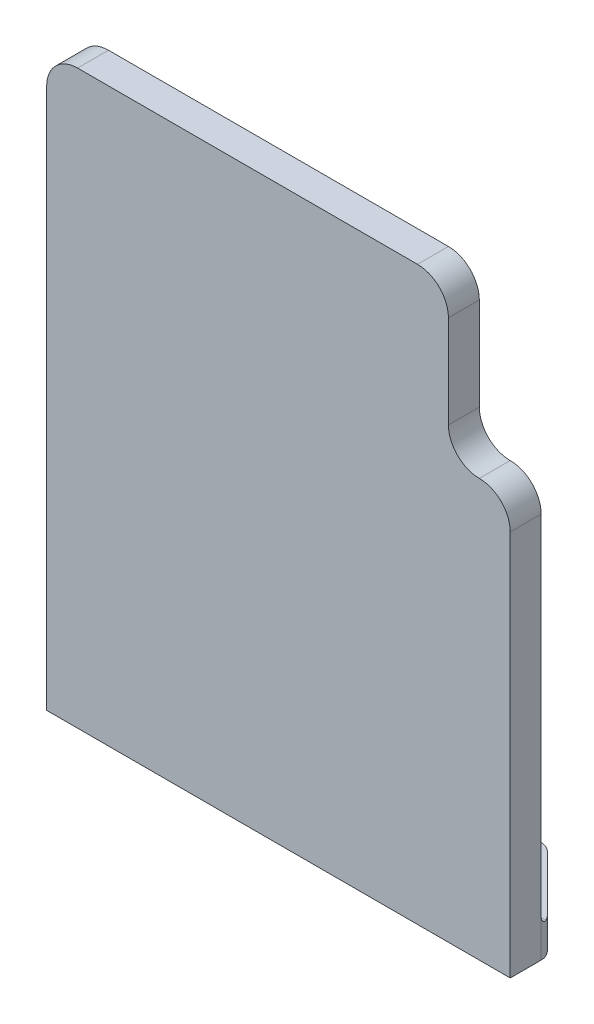
SolidWorks part; units mm, degrees
ref_plane "Front Plane" through (0, 0, 0) normal (0, 0, 1) x (1, 0, 0)
ref_plane "Top Plane" through (0, 0, 0) normal (0, 1, 0) x (1, 0, 0)
ref_plane "Right Plane" through (0, 0, 0) normal (1, 0, 0) x (0, 0, -1)
sketch "Sketch2" plane through (0, 0, 0) normal (0, 0, 1) x (1, 0, 0)
  line L1 (85, 92.5) -> (-85, 92.5)
  line L2 (85, 92.5) -> (85, -92.5)
  line L3 (85, -92.5) -> (-85, -92.5)
  line L4 (-85, 92.5) -> (-85, -92.5)
  line L5 (85, 92.5) -> (-85, -92.5) construction
  line L6 (85, -92.5) -> (-85, 92.5) construction
  point P1 (0, 0)
  dimension "D1" = 170
  dimension "D2" = 185
extrude "Boss-Extrude1" add sketch "Sketch2" against normal blind 9.8
sketch "Sketch4" plane through (0, 0, 0) normal (0, 0, 1) x (1, 0, 0)
  line L0 (85, 92.5) -> (-85, 92.5) construction
  line L1 (0, 92.5) -> (0, -92.5) construction
  line L3 (-85, -92.5) -> (85, -92.5) construction
  line L4 (20.4224, 2.5) -> (79.0575, 2.5) construction
  line L5 (50, -15) -> (50, 37.4756) construction
  line L6 (-50, -52.3549) -> (-50, 0) construction
  line L7 (-50, 2.5) -> (-27.5899, 2.5) construction
  line L8 (85, -82.5) -> (-65, -82.5) construction
  line L9 (-85, 92.5) -> (-65, 92.5)
  line L10 (-85, 92.5) -> (-85, -92.5)
  line L11 (-85, -92.5) -> (-65, -92.5)
  line L12 (-65, 92.5) -> (-65, -92.5)
  line L13 (10, -82.5) -> (-10, -82.5)
  line L14 (85, 92.5) -> (65, 92.5)
  line L15 (85, 92.5) -> (85, 42.5)
  line L16 (25, -22.5) -> (75, 27.5) construction
  line L17 (25, 27.5) -> (75, -22.5) construction
  line L18 (50, 2.5) -> (-50, 2.5) construction
  line L20 (85, 42.5) -> (65, 42.5)
  line L21 (65, 92.5) -> (65, 42.5)
  line L22 (10, -82.5) -> (10, -47.5)
  line L23 (10, -47.5) -> (-10, -47.5)
  line L24 (10, -82.5) -> (10, -112.015) construction
  line L25 (-10, -82.5) -> (-10, -47.5)
  circle A0 centre (50, 77.5) radius 3
  circle A1 centre (50, -72.5) radius 3
  circle A2 centre (-25, -22.5) radius 2.5
  circle A3 centre (-50, 77.5) radius 3
  circle A4 centre (50, 2.5) radius 20
  circle A5 centre (25, -22.5) radius 3
  circle A6 centre (-50, 62.5) radius 3
  circle A7 centre (-25, 27.5) radius 2.5
  circle A8 centre (0, 2.5) radius 20
  circle A9 centre (0, 35.8047) radius 3
  circle A10 centre (0, -30.8047) radius 3
  circle A11 centre (75, -22.5) radius 3
  circle A12 centre (75, 27.5) radius 3
  circle A13 centre (25, 27.5) radius 3
  circle A14 centre (35, -72.5) radius 3
  circle A15 centre (-50, -30.8047) radius 3
  circle A16 centre (-20, 77.5) radius 3
  circle A17 centre (20, 77.5) radius 3
  circle A18 centre (-50, 35.8047) radius 3
  circle A19 centre (-44.4468, 17.7516) radius 9
  circle A20 centre (0, 61.5) radius 13
  circle A21 centre (-46.8193, -11.5623) radius 10
  circle A22 centre (-35, -72.5) radius 3
  circle A23 centre (-33.3047, 2.5) radius 2.75
  circle A24 centre (35, -50) radius 11
  circle A25 centre (-40, -52.5) radius 12.5
  circle A26 centre (-50, -72.5) radius 3
  circle A27 centre (-35, 62.5) radius 3
  circle A28 centre (-35, 52.5) radius 3
  circle A29 centre (50, -30.8047) radius 3
  circle A30 centre (35, 77.5) radius 3
  circle A31 centre (-35, 77.5) radius 3
  circle A32 centre (65, -50) radius 11
  circle A33 centre (50, 62.5) radius 3
  circle A34 centre (50, 35.8047) radius 3
  circle A35 centre (65, -72.5) radius 3
  circle A36 centre (80, -72.5) radius 3
  circle A37 centre (-50, 52.5) radius 3
  circle A38 centre (35, 62.5) radius 3
  circle A39 centre (-20, 52.5) radius 3
  circle A40 centre (20, 52.5) radius 3
  circle A41 centre (-20, 62.5) radius 3
  circle A42 centre (20, 62.5) radius 3
  circle A43 centre (35, 52.5) radius 3
  circle A44 centre (50, 52.5) radius 3
  dimension "D3" = 20
  dimension "D7" = 50
  dimension "D8" = 2
  dimension "D10" = 20
  dimension "D9" = 18
  dimension "D13" = 55
  dimension "D17" = 50
  dimension "D18" = 2
  dimension "D19" = 2
  dimension "D21" = 2
  dimension "D23" = 22
  dimension "D24" = 2
  dimension "D11" = 25
  dimension "D12" = 2
  dimension "D14" = 31
  dimension "D15" = 26
  dimension "D16" = 50
  dimension "D20" = 6
  dimension "D1" = 10
  dimension "D4" = 20
  dimension "D5" = 10
  dimension "D6" = 35
  dimension "D22" = 2
extrude "holes" cut sketch "Sketch4" against normal up to surface (9.8 mm away) up to face at (0, 0, -9.8)
sketch "Sketch6" plane through (0, 0, -9.8) normal (0, 0, -1) x (-1, 0, 0)
  line L0 (-10, -82.5) -> (-10, -92.5)
  line L1 (-10, -92.5) -> (-10, 97.0409) construction
  line L2 (65, -92.5) -> (-85, -92.5) construction
  line L3 (10, -82.5) -> (10, -42.5)
  line L4 (65, -92.5) -> (10, -92.5)
  line L5 (0, -90) -> (0, 92.5) construction
  line L6 (65, -92.5) -> (65, -82.5)
  line L7 (65, -82.5) -> (18, -82.5)
  line L8 (-85, -92.5) -> (-85, -82.5)
  line L9 (10, -82.5) -> (10, -92.5)
  line L10 (-65, 92.5) -> (65, 92.5) construction
  line L11 (-18, -82.5) -> (-18, -42.5)
  line L12 (-18, -42.5) -> (-10, -42.5)
  line L13 (-10, -82.5) -> (-10, -42.5)
  line L14 (18, -42.5) -> (10, -42.5)
  line L15 (18, -82.5) -> (18, -42.5)
  line L16 (-10, -92.5) -> (-85, -92.5)
  line L18 (-18, -82.5) -> (-85, -82.5)
  dimension "D1" = 10
  dimension "D2" = 8
  dimension "D3" = 40
  dimension "D4" = 10
  dimension "D5" = 20
  dimension "D6" = 8
extrude "feet" add sketch "Sketch6" along normal blind 23
sketch "Sketch7" plane through (0, -92.5, 0) normal (0, -1, 0) x (1, 0, 0)
  line L2 (10, 0) -> (10, -52.2691) construction
  line L9 (-65, 0) -> (85, 0) construction
  line L10 (0, -9.8) -> (0, 0) construction
  line L11 (-10, -9.8) -> (10, -9.8) construction
  circle A0 centre (60, -25) radius 3
  circle A1 centre (30, -25) radius 3
  circle A3 centre (-30, -25) radius 3
  circle A4 centre (-60, -25) radius 3
  circle A5 centre (0, -25) radius 3 [skipped]
  dimension "D1" = 25
  dimension "D3" = 6
  dimension "D2" = 60
  dimension "D4" = 5
extrude "feet-hole" cut sketch "Sketch7" against normal up to surface (10 mm away) up to face at (-41.5, -82.5, -21.3)
sketch "Sketch9" plane through (0, 0, -9.8) normal (0, 0, -1) x (-1, 0, 0)
  line L0 (0, 92.5) -> (0, -88.6416) construction
  line L2 (-25, -22.5) -> (-75, 27.5) construction
  circle A0 centre (-75, -22.5) radius 6
  circle A1 centre (-75, -22.5) radius 3 construction
  circle A2 centre (-25, -22.5) radius 6
  circle A3 centre (-25, 27.5) radius 6
  circle A4 centre (-75, 27.5) radius 6
  circle A5 centre (-75, 27.5) radius 3 construction
  circle A6 centre (-25, 27.5) radius 3 construction
  circle A7 centre (-25, -22.5) radius 3 construction
  circle A9 centre (-50, -30.8047) radius 6
  circle A10 centre (25, 27.5) radius 6
  circle A11 centre (25, -22.5) radius 6
  circle A16 centre (25, 27.5) radius 2.5 construction
  circle A18 centre (25, -22.5) radius 2.5 construction
  circle A19 centre (-50, -30.8047) radius 3 construction
  circle A24 centre (0, -30.8047) radius 6
  circle A25 centre (-50, 35.8047) radius 6
  circle A26 centre (-50, 35.8047) radius 3 construction
  circle A27 centre (33.3047, 2.5) radius 6
  circle A28 centre (33.3047, 2.5) radius 2.75 construction
  circle A29 centre (0, 35.8047) radius 6
  circle A30 centre (0, 35.8047) radius 3 construction
  dimension "D1" = 2
extrude "motor_sink" cut sketch "Sketch9" along normal blind 4 from surface starting at face at (47, 52.5, 0)
sketch "Sketch13" plane through (0, 0, 0) normal (0, 0, 1) x (1, 0, 0)
  line L1 (-65, 92.5) -> (65, 92.5)
  line L2 (65, 92.5) -> (65, 42.5)
  line L3 (65, 42.5) -> (85, 42.5)
  line L4 (85, 42.5) -> (85, -92.5)
  line L6 (85, -92.5) -> (85, 42.5) construction
  line L7 (85, -92.5) -> (-65, -92.5)
  line L8 (-65, -92.5) -> (-65, 92.5)
extrude "Boss-Extrude2" add sketch "Sketch13" along normal blind 0.2
fillet "Fillet4" radius 10 4 edges at (65, 42.5, -4.8) (-65, 92.5, -4.8) (85, 42.5, -4.8) (65, 92.5, -4.8)
sketch "Sketch14" plane through (18, 0, 0) normal (1, 0, 0) x (0, 0, -1)
  line L0 (32.8, -82.5) -> (9.8, -42.5)
  line L1 (9.8, -42.5) -> (32.8, -42.5)
  line L2 (32.8, -42.5) -> (32.8, -82.5)
extrude "Cut-Extrude2" cut sketch "Sketch14" against normal through all
fillet "Fillet6" radius 2 4 edges at (14, -42.5, -9.8) (-14, -42.5, -9.8) (-41.5, -82.5, -9.8) (51.5, -82.5, -9.8)
sketch "Sketch16" plane through (0, -82.5, 0) normal (0, 1, 0) x (1, 0, 0)
  line L0 (85, 11.8) -> (64, 32.8)
  line L1 (18, 32.8) -> (85, 32.8) construction
  line L2 (85, 11.8) -> (85, 32.8)
  line L3 (85, 32.8) -> (64, 32.8)
extrude "Cut-Extrude3" cut sketch "Sketch16" against normal through all
fillet "Fillet7" radius 5 3 edges at (85, -87.5, -11.8) (64, -87.5, -32.8) (-65, -87.5, -32.8)
